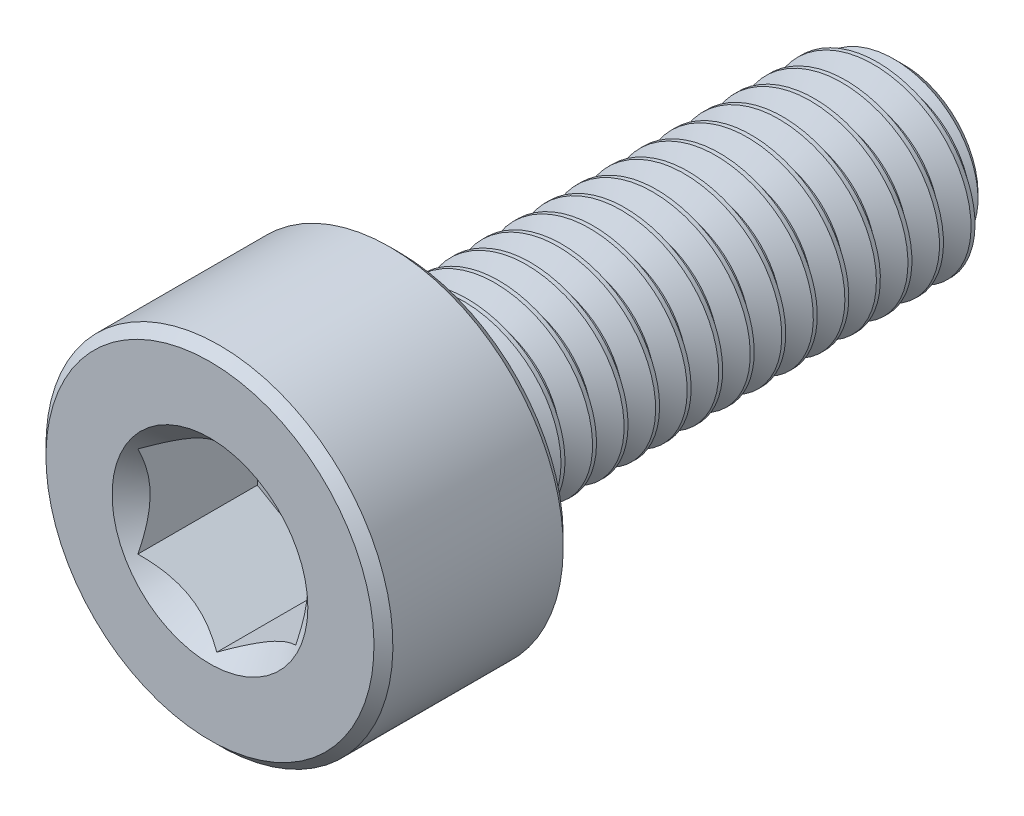
SolidWorks part; units mm, degrees
material "Alloy Steel"
ref_plane "Front Plane" through (0, 0, 0) normal (0, 0, 1) x (1, 0, 0)
ref_plane "Top Plane" through (0, 0, 0) normal (0, 1, 0) x (1, 0, 0)
ref_plane "Right Plane" through (0, 0, 0) normal (1, 0, 0) x (0, 0, -1)
sketch "Sketch1" plane through (0, 0, 0) normal (1, 0, 0) x (0, 0, -1)
  line L0 (-5.5, 0) -> (5.5, 0) construction
  line L1 (5.5, 0) -> (5.5, 1.1752) construction
  line L2 (5.5, 1.1752) -> (5.1752, 1.5) construction
  line L3 (5.1752, 1.5) -> (5.125, 1.5) construction
  line L4 (5.125, 1.5) -> (-2.5, 1.5) construction
  line L5 (-2.5, 1.5) -> (-2.5, 2.75) construction
  line L6 (-2.5, 2.75) -> (-5.5, 2.75) construction
  line L7 (-5.5, 2.75) -> (-5.5, 0) construction
  line L8 (5.5, 1.1752) -> (5.5, 1.5) construction
  line L9 (5.4688, 1.5541) -> (5.7188, 1.1211) construction
  line L10 (5.7188, 1.1211) -> (5.9688, 1.5541) construction
  line L11 (5.9688, 1.5541) -> (5.4688, 1.5541) construction
  line L12 (5.7188, 1.5541) -> (5.7188, 1.5) construction
  line L13 (5.7188, 1.1211) -> (5.7188, 1.1752) construction
  line L14 (5.6875, 1.1752) -> (5.75, 1.1752) construction
  line L15 (5.5, 1.5) -> (5.9375, 1.5) construction
  line L16 (5.4844, 1.5271) -> (5.9531, 1.5271) construction
  line L17 (5.5, 0) -> (5.5, -1.5) construction
  line L18 (-2.65, 2.75) -> (-2.5, 2.6) construction
  line L19 (-5.35, 2.75) -> (-5.5, 2.6) construction
  line L20 (-2.5, 1.5) -> (-2.5, 0) construction
  line L21 (-2.5, 0.75) -> (0.1667, 0.75) construction
  line L22 (0.1667, 0.75) -> (2.8333, 0.75) construction
  line L23 (2.8333, 0.75) -> (5.5, 0.75) construction
  line L24 (0.1667, 0.75) -> (0.1667, 1.5) construction
  line L25 (0.1667, 1.5) -> (0.1667, 2.75) construction
  line L26 (2.8333, 0.75) -> (2.8333, 2.75) construction
  point P0 (-5.5, 1.25)
  point P3 (4.25, 1.5)
  point P4 (0, 0)
  point P18 (2.8333, 1.5)
  point P22 (5.7188, 1.1752)
  point P24 (5.125, 1.5)
  point P25 (5.7188, 1.5)
  point P28 (5.7188, 1.5271)
  point P29 (4.25, -1.5)
  point P30 (0.1667, 1.5)
  point P31 (-4, 2.75)
  point P37 (-3.025, 2.75)
  point P38 (-5.275, 2.75)
  point P45 (0.1667, 0.75)
  point P46 (2.8333, 0.75)
  dimension "D2" = 0.0625
  dimension "D7" = 0.15
  dimension "D8" = 0.15
  dimension "D9" = 0.15
  dimension "D10" = 0.075
  dimension "D11" = 0.375
  dimension "Drive Size" = 2.5
  dimension "Head Diameter" = 5.5
  dimension "Head Height" = 3
  dimension "Thread Pitch" = 0.5
  dimension "Thread Size" = 3
  dimension "Length" = 8
  dimension "D12" = 0.375
  dimension "D4" = 1.25
  dimension "D3" = 45
sketch "Sketch2" plane through (0, 0, 0) normal (1, 0, 0) x (0, 0, -1)
  line L0 (-5.5, 0) -> (-5.5, 2.6)
  line L1 (-5.35, 2.75) -> (-2.65, 2.75)
  line L2 (-2.5, 2.6) -> (-2.5, 1.65)
  line L4 (5.1752, 1.5) -> (5.5, 1.1752)
  line L5 (5.5, 1.1752) -> (5.5, 0)
  line L6 (-2.5, 2.75) -> (-5.5, 2.75) construction
  line L7 (5.5, 0) -> (-5.5, 0)
  line L8 (-5.35, 2.75) -> (-5.5, 2.6) construction
  line L10 (-5.35, 2.75) -> (-5.5, 2.6)
  line L14 (-2.65, 2.75) -> (-2.5, 2.6) construction
  line L16 (-2.65, 2.75) -> (-2.5, 2.6)
  line L17 (-2.5, 1.5) -> (-2.5, 2.75) construction
  line L19 (-2.35, 1.5) -> (5.1752, 1.5)
  line L20 (5.125, 1.5) -> (-2.5, 1.5) construction
  arc A1 (-2.5, 1.65) -> (-2.35, 1.5) centre (-2.35, 1.65) ccw
  dimension "D3" = 0.15
revolve "Revolve1" add sketch "Sketch2" angle 360 about L7
sketch "Sketch3" plane through (0, 0, 5.5) normal (0, 0, 1) x (1, 0, 0)
  line L1 (1.25, -0.7217) -> (1.25, 0.7217)
  line L2 (1.25, 0.7217) -> (0, 1.4434)
  line L3 (0, 1.4434) -> (-1.25, 0.7217)
  line L4 (-1.25, 0.7217) -> (-1.25, -0.7217)
  line L5 (-1.25, -0.7217) -> (0, -1.4434)
  line L6 (0, -1.4434) -> (1.25, -0.7217)
  circle A0 centre (0, 0) radius 1.25 construction
  circle A1 centre (0, 0) radius 2.75 construction
  circle A2 centre (0, 0) radius 2.75 construction
  circle A3 centre (0, 0) radius 1.4434 construction
  point P13 (0, 0)
  dimension "D1" = 2.8868
extrude "Cut-Extrude1" cut sketch "Sketch3" against normal offset from surface (2 mm away) 1 up to face at (0, 2.6, 2.5)
sketch "Sketch4" plane through (0, 0, 5.5) normal (0, 0, 1) x (1, 0, 0)
  circle A0 centre (0, 0) radius 1.5516
  dimension "D1" = 3.1033
extrude "Cut-Extrude2" cut sketch "Sketch4" against normal up to vertex (1.5 mm away) draft 45 up to point (0, 2.75, 4)
sketch "Sketch11" plane through (0, 0, 0) normal (1, 0, 0) x (0, 0, -1)
  line L0 (-5.5, 0) -> (5.5, 0) construction
  line L1 (-5.5, 0) -> (5.5, 0) construction
  line L2 (-1, 0) -> (-1, 1.5) construction
  line L3 (5.125, 1.5) -> (-2.5, 1.5) construction
  line L4 (4, 0) -> (4, 1.5) construction
  line L6 (5.5, 1.1752) -> (5.5, 1.5) construction
  point P2 (-1, 0)
  point P3 (4, 0)
  dimension "D1" = 1.5
  dimension "D2" = 1.5
sketch "Sketch6" plane through (0, 0, -5.5) normal (0, 0, -1) x (-1, 0, 0)
  circle A0 centre (0, 0) radius 1.5
curve "Helix/Spiral1" pitch 0.5 height 8.5 radius 1.5 centre (0, 0, -5.5) axis (0, 0, 1) start towards (0, 1, 0)
sketch "Sketch10" plane through (0, 0, 0) normal (1, 0, 0) x (0, 0, -1)
  line L0 (-2.35, -2.75) -> (-2.35, 2.75)
  line L5 (-5.5, 0) -> (5.5, 0) construction
  line L6 (-2.35, 1.5) -> (-2.35, -1.5) construction
  point P3 (-2.35, 0)
split "Split1" trim tools "Sketch10" bodies to split 106 resulting bodies 114 115
sketch "Sketch7" plane through (0, 0, 0) normal (1, 0, 0) x (0, 0, -1)
  line L0 (5.4844, 1.5271) -> (5.9531, 1.5271)
  line L1 (5.9531, 1.5271) -> (5.75, 1.1752)
  line L2 (5.75, 1.1752) -> (5.6875, 1.1752)
  line L3 (5.6875, 1.1752) -> (5.4844, 1.5271)
sweep "Cut-Sweep1" cut profiles "Sketch7" path "Helix/Spiral1" align with end faces yes
sketch "Sketch8" plane through (0, 0, 0) normal (1, 0, 0) x (0, 0, -1)
  line L0 (-2.5, 0) -> (-2.5, 1.5)
  line L1 (-2.35, -1.5) -> (-2.35, 1.5) construction
  line L2 (-2.5, 1.5) -> (-2.35, 1.5)
  line L4 (-2.35, 1.5) -> (-1.484, 0)
  line L5 (-1.484, 0) -> (-2.5, 0)
  line L6 (5.125, 1.5) -> (-2.5, 1.5) construction
  line L7 (-5.5, 0) -> (5.5, 0) construction
  dimension "D1" = 60
revolve "Revolve2" add sketch "Sketch8" angle 360 about L5
equation "\"D2@Sketch1\" = \"Thread Pitch@Sketch1\" / 8"
equation "\"D4@Helix/Spiral1\" = \"Thread Pitch@Sketch1\""
equation "\"D7@Sketch1\" = \"Head Height@Sketch1\" * .05"
equation "\"D8@Sketch1\"=\"D7@Sketch1\""
equation "\"D9@Sketch1\"=\"D7@Sketch1\""
equation "\"D10@Sketch1\"=\"D7@Sketch1\"/2"
equation "\"D11@Sketch1\"=\"D10@Sketch1\"*5"
equation "\"D4@Sketch1\"=\"Thread Pitch@Sketch1\"*2.5"
equation "\"D12@Sketch1\"=\"Thread Pitch@Sketch1\"*.75"
equation "\"D3@Helix/Spiral1\"=\"Length@Sketch1\"+\"Thread Pitch@Sketch1\""
equation "\"D3@Sketch2\"=\"Thread Size@Sketch1\"*0.05"
equation "\"D1@Sketch11\"=\"Length@Sketch1\"*0.1875"
equation "\"D2@Sketch11\"=\"D1@Sketch11\""
equation "\"D1@Sketch4\"=\"D1@Sketch3\"*1.075"
